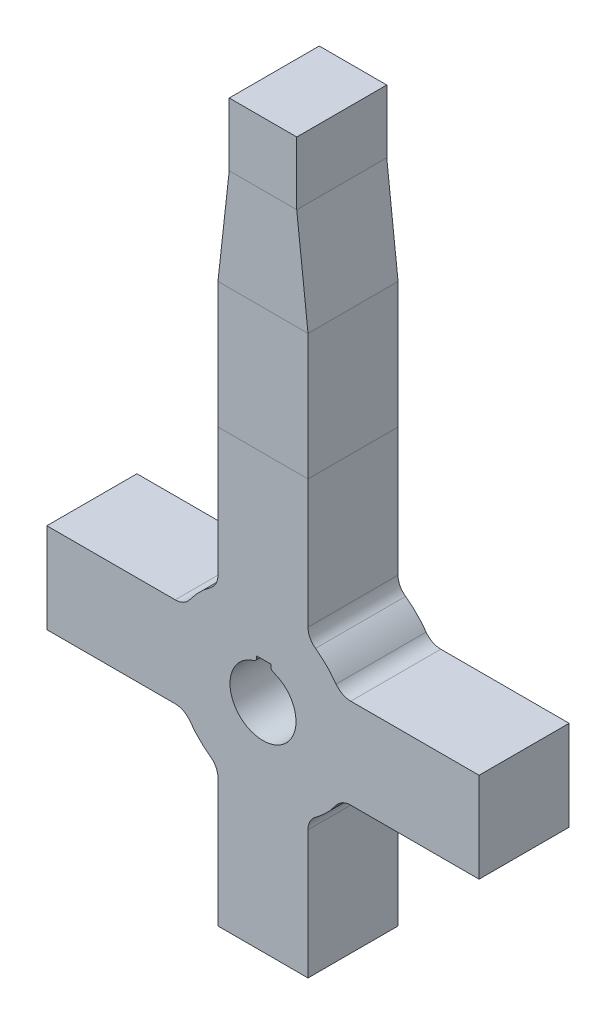
SolidWorks part; units mm, degrees
note: The reader was unsure of these and kept them because the rebuilt part matched: shared geometry of "Sketch2<3>".
ref_plane "Front Plane" through (0, 0, 0) normal (0, 0, 1) x (1, 0, 0)
ref_plane "Top Plane" through (0, 0, 0) normal (0, 1, 0) x (1, 0, 0)
ref_plane "Right Plane" through (0, 0, 0) normal (1, 0, 0) x (0, 0, -1)
sketch "Sketch2" plane through (0, 0, 0) normal (0, 0, 1) x (1, 0, 0)
  line L4 (0, 0) -> (-106.8478, 0) construction
  line L27 (0, 25) -> (-120, 25)
  line L28 (0, 25) -> (0, -25)
  line L29 (0, -25) -> (-120, -25)
  line L30 (-120, 25) -> (-120, -25)
  circle A9 centre (0, 0) radius 50
  point P1 (-79.5807, 0)
  point P8 (0, 0)
  point P9 (0, 0)
  dimension "D1" = 100
  dimension "D2" = 50
  dimension "D3" = 120
extrude "Boss-Extrude1" add sketch "Sketch2" along normal blind 50
extrude "Boss-Extrude2" add sketch "Sketch2<3>" along normal blind 50
sketch "Sketch2<3>" plane through (0, 0, 0) normal (0, 0, 1) x (1, 0, 0) same geometry as "Sketch2"
fillet "Fillet1" radius 10 2 edges at (-43.3013, -25, 25) (-43.3013, 25, 25)
pattern_circular "CirPattern1" count 4 over 360 about axis through (0, 0, 0) along (0, 0, 1) of "Boss-Extrude2", "Fillet1"
sketch "Sketch3" plane through (0, 0, 50) normal (0, 0, 1) x (1, 0, 0)
  line L0 (-3.6293, 19.5314) -> (-3.6293, 20.6534)
  line L1 (-3.6293, 20.6534) -> (4.4263, 20.6534)
  line L2 (4.4263, 20.6534) -> (4.4263, 19.2839)
  arc A0 (-5.0754, 17.6097) -> (5.7939, 17.3865) centre (0, 0) ccw
  arc A1 (4.4263, 19.2839) -> (5.7939, 17.3865) centre (6.4263, 19.2839) ccw
  arc A2 (-5.0754, 17.6097) -> (-3.6293, 19.5314) centre (-5.6293, 19.5314) ccw
  dimension "D1" = 2
extrude "Cut-Extrude1" cut sketch "Sketch3" against normal through all
sketch "Sketch11" plane through (-25, 0, 0) normal (-1, 0, 0) x (0, 0, 1)
  line L0 (0, 120) -> (50, 120)
  line L1 (50, 120) -> (50, 190)
  line L2 (0, 120) -> (0, 190)
  line L3 (0, 190) -> (50, 190)
  dimension "D2" = 50
  dimension "D1" = 70
extrude "Boss-Extrude7" add sketch "Sketch11" against normal up to vertex (50 mm away) separate body
sketch "Sketch13" plane through (0, 0, 0) normal (0, 0, -1) x (-1, 0, 0)
  line L0 (-25, 190) -> (25, 190)
  line L1 (25, 190) -> (18.75, 246.334)
  line L2 (18.75, 246.334) -> (-18.75, 246.334)
  line L3 (-18.75, 246.334) -> (-25, 190)
  dimension "D1" = 37.5
extrude "Boss-Extrude8" add sketch "Sketch13" against normal up to vertex (50 mm away) separate body
sketch "Sketch14" plane through (0, 0, 0) normal (0, 0, -1) x (-1, 0, 0)
  line L0 (-18.75, 246.334) -> (18.75, 246.334)
  line L1 (18.75, 246.334) -> (18.75, 281.334)
  line L2 (18.75, 281.334) -> (-18.75, 281.334)
  line L3 (-18.75, 281.334) -> (-18.75, 246.334)
  dimension "D1" = 35
extrude "Boss-Extrude9" add sketch "Sketch14" against normal up to vertex (50 mm away) separate body
equation "\"Base_circle\"= 100"
equation "\"base_arm_width\"= 50"
equation "\"base_arm_length\"= 120"
equation "\"circle_base_arm\"= 10"
equation "\"stress_distance_base_arm_circle\"= \"circle_base_arm\" / 3 + \"circle_base_arm\" / 2"
equation "\"D1@Sketch2\"=\"Base_circle\""
equation "\"D2@Sketch2\"=\"base_arm_width\""
equation "\"D3@Sketch2\"=\"base_arm_length\""
equation "\"depth\"= 50"
equation "\"D1@Boss-Extrude1\"=\"depth\""
equation "\"D1@Boss-Extrude2\"=\"depth\""
equation "\"gear_house_a\"= 70"
equation "\"gear_house_b\"= 35"
equation "\"D1@Sketch11\"=\"gear_house_a\""
equation "\"D2@Sketch11\"=\"depth\""
equation "\"D1@Sketch13\"=\"depth\"*0.75"
equation "\"D1@Sketch14\"=\"gear_house_b\""
